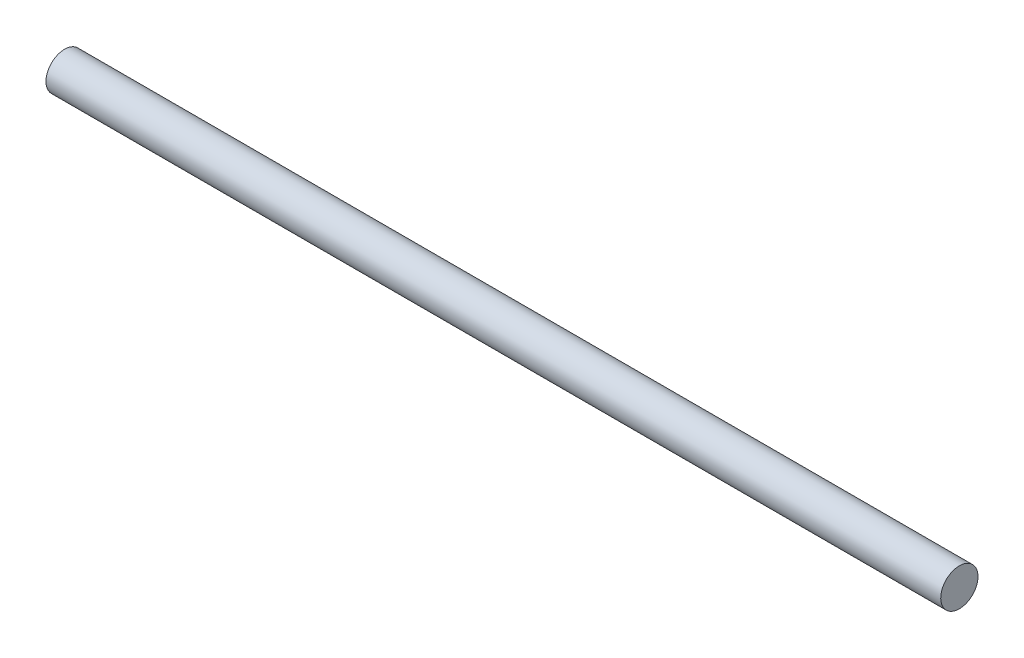
SolidWorks part; units mm, degrees
ref_plane "Front" through (0, 0, 0) normal (0, 0, 1) x (1, 0, 0)
ref_plane "Top" through (0, 0, 0) normal (0, 1, 0) x (1, 0, 0)
ref_plane "Right" through (0, 0, 0) normal (1, 0, 0) x (0, 0, -1)
sketch "Sketch1" plane through (0, 0, 0) normal (0, 0, -1) x (-1, 0, 0)
  line L0 (0, 0) -> (0, -0.5) construction
  line L1 (0, 0) -> (12, 0)
  line L2 (0, 0) -> (0, 0.5)
  line L3 (0, 0.5) -> (12, 0.5)
  line L4 (12, 0) -> (12, 0.5)
  dimension "Shaft Length" = 12
  dimension "Diameter" = 1
revolve "Revolve1" add sketch "Sketch1" angle 360 about L1
ref_axis "Center Axis" through (-12, 0, 0) along (1, 0, 0)
sketch "Sketch2" plane through (0, 0, 0) normal (1, 0, 0) x (0, 0, -1)
  circle A0 centre (0, 0) radius 0.5
  circle A1 centre (0, 0) radius 0.5 construction
sketch "Sketch3" plane through (0, 0, 0) normal (0, 0, 1) x (1, 0, 0)
  line L0 (0, 0) -> (0, 0.5)
  line L1 (0, 0.5) -> (12, 0.5)
  line L2 (12, 0.5) -> (12, 0)
  line L3 (12, 0) -> (0, 0)
  line L4 (0, 0.5) -> (-12, 0.5) construction
revolve "Revolve2" add sketch "Sketch3" angle 360 about L3
